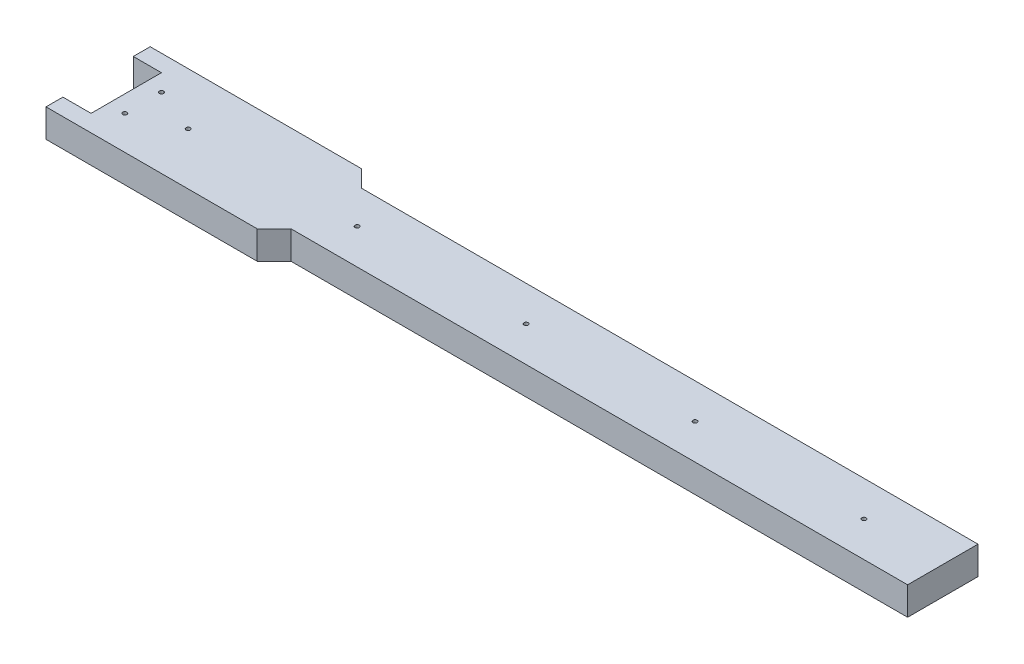
SolidWorks part; units mm, degrees
material "Сосна"
ref_plane "Спереди" through (0, 0, 0) normal (0, 0, 1) x (1, 0, 0)
ref_plane "Сверху" through (0, 0, 0) normal (0, 1, 0) x (1, 0, 0)
ref_plane "Справа" through (0, 0, 0) normal (1, 0, 0) x (0, 0, -1)
sketch "Эскиз1" plane through (0, 0, 0) normal (0, 1, 0) x (1, 0, 0)
  line L0 (0, 31) -> (75, 31)
  line L1 (75, 31) -> (81, 25)
  line L2 (81, 25) -> (300, 25)
  line L3 (300, 25) -> (300, 0)
  line L4 (300, 0) -> (81, 0)
  line L5 (81, 0) -> (75, -6)
  line L6 (75, -6) -> (0, -6)
  line L7 (0, -6) -> (0, 0)
  line L8 (0, 0) -> (10, 0)
  line L9 (10, 0) -> (10, 25)
  line L10 (10, 25) -> (0, 25)
  line L11 (0, 25) -> (0, 31)
  dimension "D1" = 300
  dimension "D2" = 75
  dimension "D3" = 25
  dimension "D4" = 25
  dimension "D5" = 37
  dimension "D6" = 10
extrude "Бобышка-Вытянуть1" add sketch "Эскиз1" along normal blind 10
sketch "Эскиз2" plane through (0, 10, 0) normal (0, 1, 0) x (1, 0, 0)
  line L0 (0, 31) -> (0, 25) construction
  line L1 (75, 31) -> (0, 31) construction
  circle A0 centre (32, 12.5) radius 0.75
  dimension "D1" = 1.5
  dimension "D2" = 32
  dimension "D3" = 18.5
extrude "Вырез-Вытянуть1" cut sketch "Эскиз2" against normal through all
pattern_linear "Линейный массив1" count 5 spacing 60 along (1, 0, 0) of "Вырез-Вытянуть1"
sketch "Эскиз4" plane through (0, 10, 0) normal (0, 1, 0) x (1, 0, 0)
  line L0 (0, 0) -> (0, -6) construction
  line L1 (0, -6) -> (75, -6) construction
  circle A0 centre (16, 6) radius 0.75
  circle A1 centre (16, 19) radius 0.75
  dimension "D1" = 1.5
  dimension "D2" = 16
  dimension "D3" = 12
  dimension "D4" = 2
extrude "Вырез-Вытянуть2" cut sketch "Эскиз4" against normal through all
